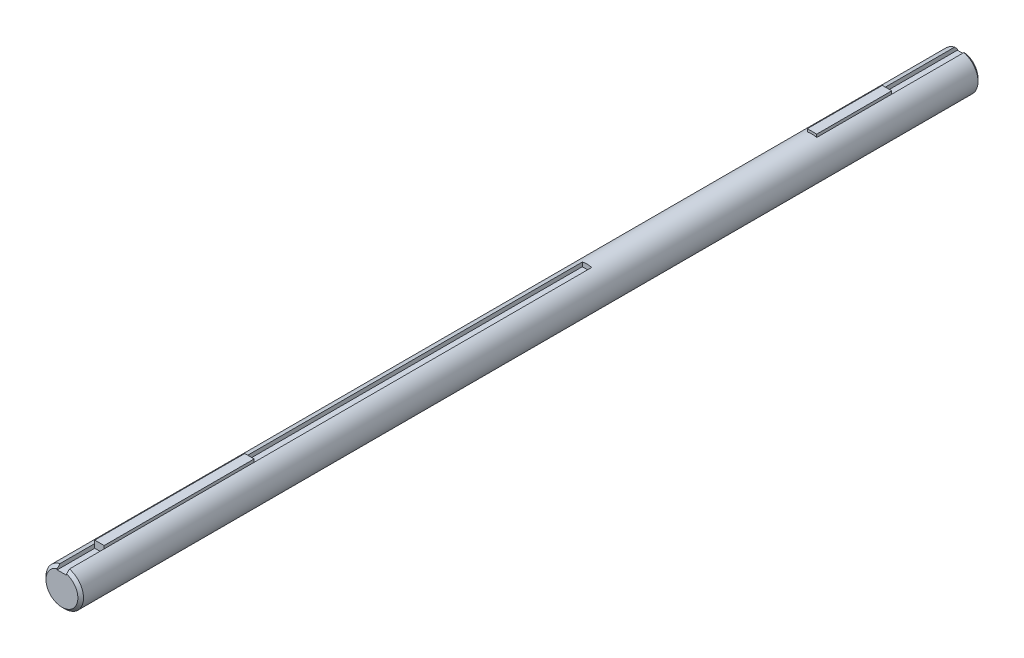
SolidWorks part; units mm, degrees
ref_plane "Front" through (0, 0, 0) normal (0, 0, 1) x (1, 0, 0)
ref_plane "Top" through (0, 0, 0) normal (0, 1, 0) x (1, 0, 0)
ref_plane "Right" through (0, 0, 0) normal (1, 0, 0) x (0, 0, -1)
sketch "Sketch1" plane through (0, 0, 0) normal (0, 0, 1) x (1, 0, 0)
  circle A0 centre (0, 0) radius 12.7
  dimension "dia" = 25.4
extrude "Extrude1" add sketch "Sketch1" along normal mid plane 609.6
sketch "Sketch2" plane through (0, 0, 0) normal (1, 0, 0) x (0, 0, -1)
  point P0 (-304.8, 12.7)
  point P1 (304.8, 12.7)
  point P2 (304.8, -12.7)
chamfer "Chamfer1" distance 1.905 angle 45 2 edges at (12.7, 0, -304.8) (12.7, 0, 304.8)
sketch "Sketch3" plane through (0, 0, 0) normal (0, 0, 1) x (1, 0, 0)
  line L1 (-3.175, 12.7) -> (3.175, 12.7)
  line L2 (-3.175, 12.7) -> (-3.175, 9.525)
  line L3 (-3.175, 9.525) -> (3.175, 9.525)
  line L4 (3.175, 12.7) -> (3.175, 9.525)
  dimension "key wd" = 6.35
  dimension "key dp" = 3.175
extrude "Extrude2" cut sketch "Sketch3" against normal through all and the other way through all
extrude "Extrude3" add sketch "Sketch1<2>" along normal offset from surface 355.6 and the other way offset from surface 101.6 from offset 101.6 up to face at (0, 4.6431, 304.8) other way up to face at (0, 4.6431, -304.8) offset against normal yes
sketch "Sketch1<2>" plane through (0, 0, 0) normal (0, 0, 1) x (1, 0, 0) same geometry as "Sketch1"
ref_plane "Plane1" through (0, 0, 228.6) normal (0, 0, 1) x (1, 0, 0)
ref_plane "Plane2" through (0, 0, -228.6) normal (0, 0, -1) x (-1, 0, 0)
sketch "Sketch5" plane through (0, 0, 228.6) normal (0, 0, 1) x (1, 0, 0)
  line L1 (3.175, 12.7) -> (3.175, 9.525) construction
  line L2 (-3.175, 9.525) -> (3.175, 9.525) construction
  line L3 (-3.175, 12.7) -> (-3.175, 9.525) construction
  line L4 (-3.175, 14.2875) -> (3.175, 14.2875)
  line L5 (3.175, 14.2875) -> (3.175, 9.525)
  line L6 (-3.175, 9.525) -> (3.175, 9.525)
  line L7 (-3.175, 14.2875) -> (-3.175, 9.525)
  dimension "D1" = 4.7625
extrude "Extrude4" add sketch "Sketch5" along normal mid plane 101.6 separate body
sketch "Sketch6" plane through (0, 0, -228.6) normal (0, 0, -1) x (-1, 0, 0)
  line L4 (3.175, 14.2875) -> (-3.175, 14.2875)
  line L5 (-3.175, 14.2875) -> (-3.175, 9.525)
  line L6 (-3.175, 9.525) -> (3.175, 9.525)
  line L7 (3.175, 9.525) -> (3.175, 14.2875)
  line L8 (3.175, 14.2875) -> (-3.175, 14.2875)
  line L9 (-3.175, 14.2875) -> (-3.175, 9.525)
  line L10 (-3.175, 9.525) -> (3.175, 9.525)
  line L11 (3.175, 9.525) -> (3.175, 14.2875)
  dimension "D1" = 0
extrude "Extrude5" add sketch "Sketch6" along normal mid plane 50.8 separate body
equation "\"D1@Chamfer1\" = \"dia@Sketch1\" * .075"
equation "\"D1@Sketch5\" = \"key dp@Sketch3\" * 1.5"
